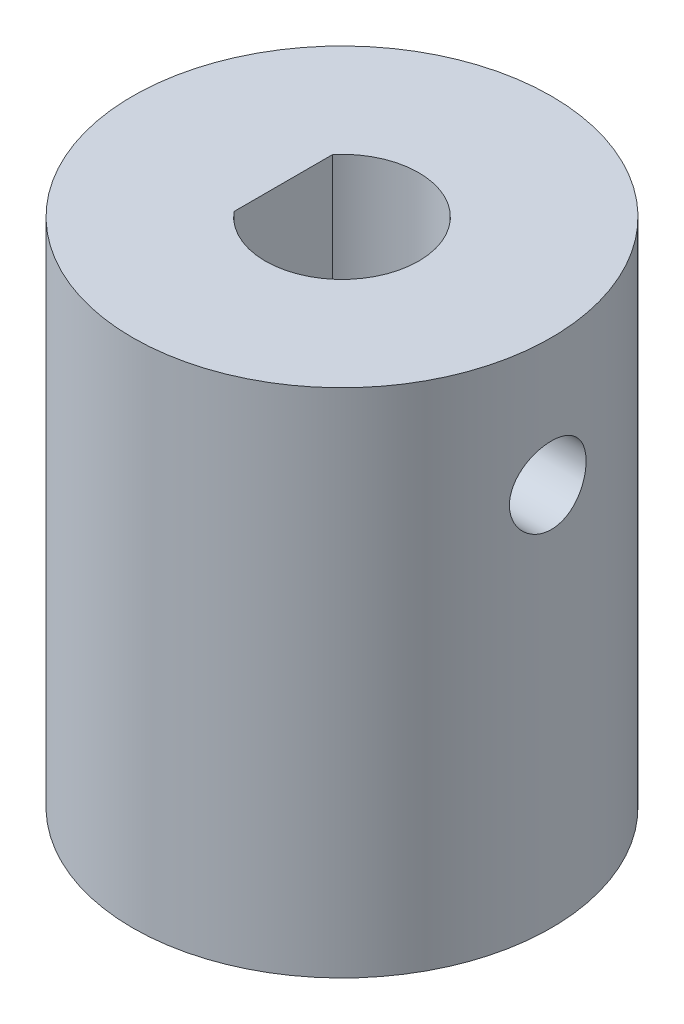
SolidWorks part; units mm, degrees
ref_plane "Front Plane" through (0, 0, 0) normal (0, 0, 1) x (1, 0, 0)
ref_plane "Top Plane" through (0, 0, 0) normal (0, 1, 0) x (1, 0, 0)
ref_plane "Right Plane" through (0, 0, 0) normal (1, 0, 0) x (0, 0, -1)
sketch "Sketch1" plane through (0, 0, 0) normal (0, 1, 0) x (1, 0, 0)
  circle A0 centre (0, 0) radius 8.189
extrude "Boss-Extrude1" add sketch "Sketch1" along normal blind 20
sketch "Sketch2" plane through (0, 20, 0) normal (0, 1, 0) x (1, 0, 0)
  circle A0 centre (0, 0) radius 3
extrude "Cut-Extrude1" cut sketch "Sketch2" against normal blind 30
sketch "Sketch4" plane through (0, 20, 0) normal (0, 1, 0) x (1, 0, 0)
  line L1 (-2.2951, -1.932) -> (-4.1343, -1.932)
  line L2 (-2.2951, -1.932) -> (-2.2951, 2.2587)
  line L3 (-2.2951, 2.2587) -> (-4.1343, 2.2587)
  line L4 (-4.1343, -1.932) -> (-4.1343, 2.2587)
  circle A0 centre (0, 0) radius 3 construction
extrude "Boss-Extrude2" add sketch "Sketch4" against normal blind 10
sketch "Sketch3" plane through (0, 0, 0) normal (1, 0, 0) x (0, 0, -1)
  circle A0 centre (0, 15) radius 1.5
extrude "Cut-Extrude2" cut sketch "Sketch3" against normal blind 10 and the other way blind 10
